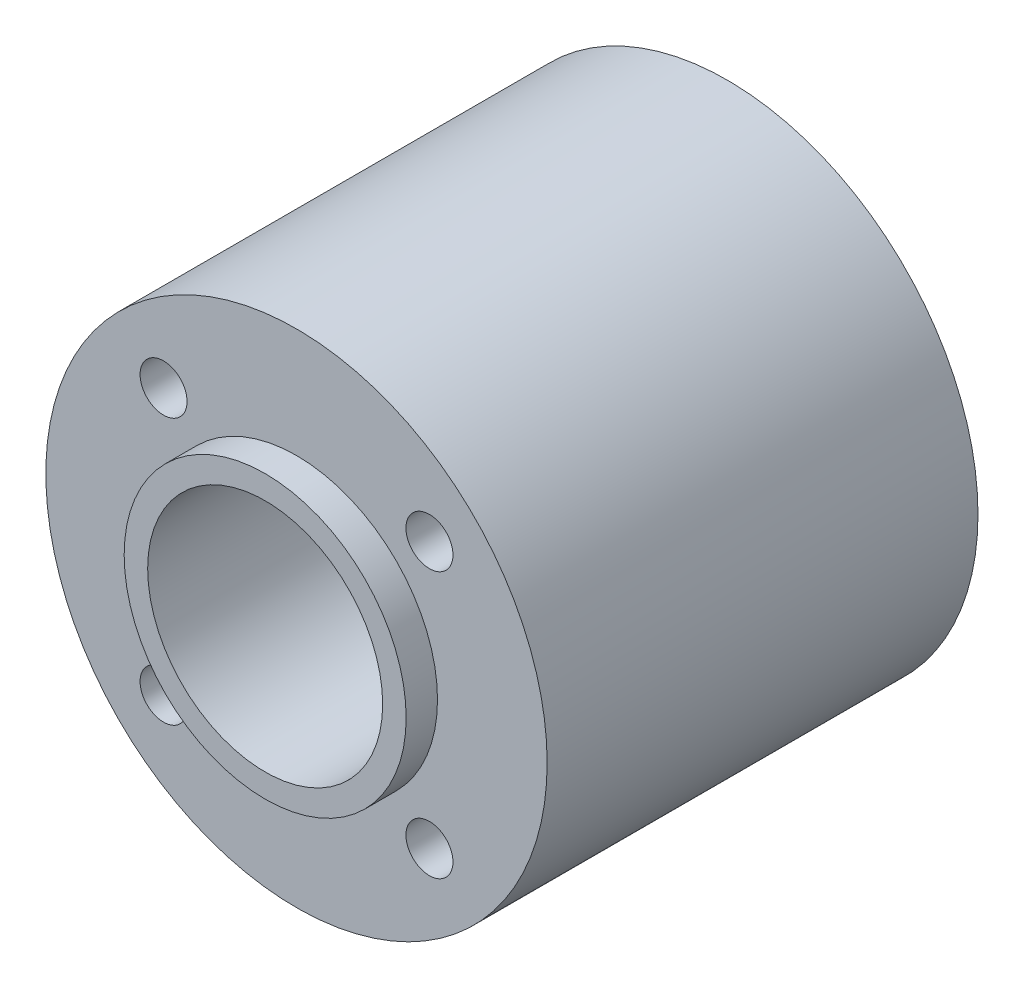
SolidWorks part; units mm, degrees
ref_plane "Front Plane" through (0, 0, 0) normal (0, 0, 1) x (1, 0, 0)
ref_plane "Top Plane" through (0, 0, 0) normal (0, 1, 0) x (1, 0, 0)
ref_plane "Right Plane" through (0, 0, 0) normal (1, 0, 0) x (0, 0, -1)
sketch "Sketch1" plane through (0, 0, 0) normal (0, 0, 1) x (1, 0, 0)
  circle A0 centre (0, 0) radius 16
  circle A1 centre (0, 0) radius 9
  circle A2 centre (0, 0) radius 7.5
  dimension "D1" = 32
  dimension "D2" = 18
  dimension "D3" = 15
extrude "Boss-Extrude1" add sketch "Sketch1" against normal blind 27.5 contours A0 A1 | A1 A2 region at (-15.5475, 0, 0) region at (-8.7454, 0, 0)
extrude "Boss-Extrude2" add sketch "Sketch1<3>" along normal blind 2 contours A1 A2 region at (-8.7454, 0, 0)
sketch "Sketch1<3>" plane through (0, 0, 0) normal (0, 0, 1) x (1, 0, 0) same geometry as "Sketch1"
extrude "Boss-Extrude3" add sketch "Sketch1<4>" against normal blind 2 from surface contours A1 | A2 starting at face at (16, 0, -27.5)
sketch "Sketch1<4>" plane through (0, 0, 0) normal (0, 0, 1) x (1, 0, 0) same geometry as "Sketch1"
sketch "Sketch2" plane through (0, 0, 0) normal (0, 0, 1) x (1, 0, 0)
  line L0 (0, 12) -> (0, 0) construction
  line L1 (0, 0) -> (-8.4853, 8.4853) construction
  circle A0 centre (0, 0) radius 12 construction
  circle A1 centre (-8.4853, 8.4853) radius 1.5
  circle A2 centre (8.4853, 8.4853) radius 1.5
  circle A3 centre (8.4853, -8.4853) radius 1.5
  circle A4 centre (-8.4853, -8.4853) radius 1.5
  point P15 (0, 0)
  dimension "D1" = 45
  dimension "D2" = 4
extrude "Cut-Extrude1" cut sketch "Sketch2" against normal through all
